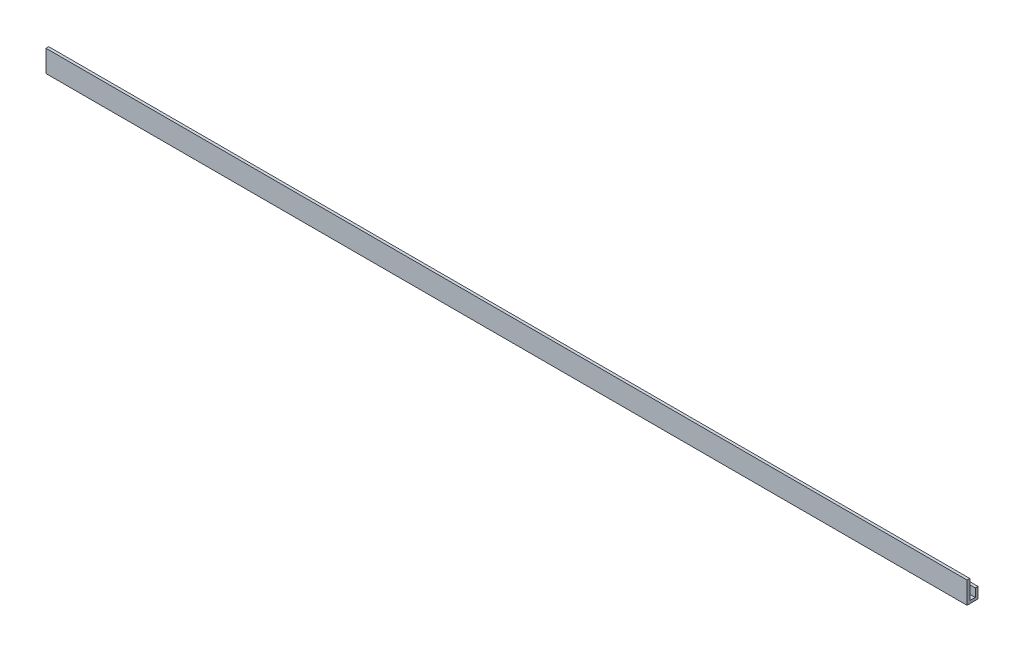
SolidWorks part; units mm, degrees
ref_plane "Front Plane" through (0, 0, 0) normal (0, 0, 1) x (1, 0, 0)
ref_plane "Top Plane" through (0, 0, 0) normal (0, 1, 0) x (1, 0, 0)
ref_plane "Right Plane" through (0, 0, 0) normal (1, 0, 0) x (0, 0, -1)
sketch "Sketch1" plane through (0, 0, 0) normal (1, 0, 0) x (0, 0, -1)
  line L0 (0, 0) -> (0, 11.1125)
  line L1 (0, 11.1125) -> (-1.5875, 11.1125)
  line L2 (-1.5875, 11.1125) -> (-1.5875, -1.5875)
  line L3 (-1.5875, -1.5875) -> (4.7625, -1.5875)
  line L4 (4.7625, -1.5875) -> (4.7625, 4.7625)
  line L5 (4.7625, 4.7625) -> (3.175, 4.7625)
  line L6 (3.175, 4.7625) -> (3.175, 0)
  line L7 (3.175, 0) -> (0, 0)
  line L8 (0, 0) -> (0, -1.5875) construction
  dimension "D1" = 1.5875
  dimension "D2" = 6.35
  dimension "D3" = 12.7
  dimension "D4" = 6.35
extrude "Boss-Extrude1" add sketch "Sketch1" along normal blind 266.7 and the other way blind 266.7
